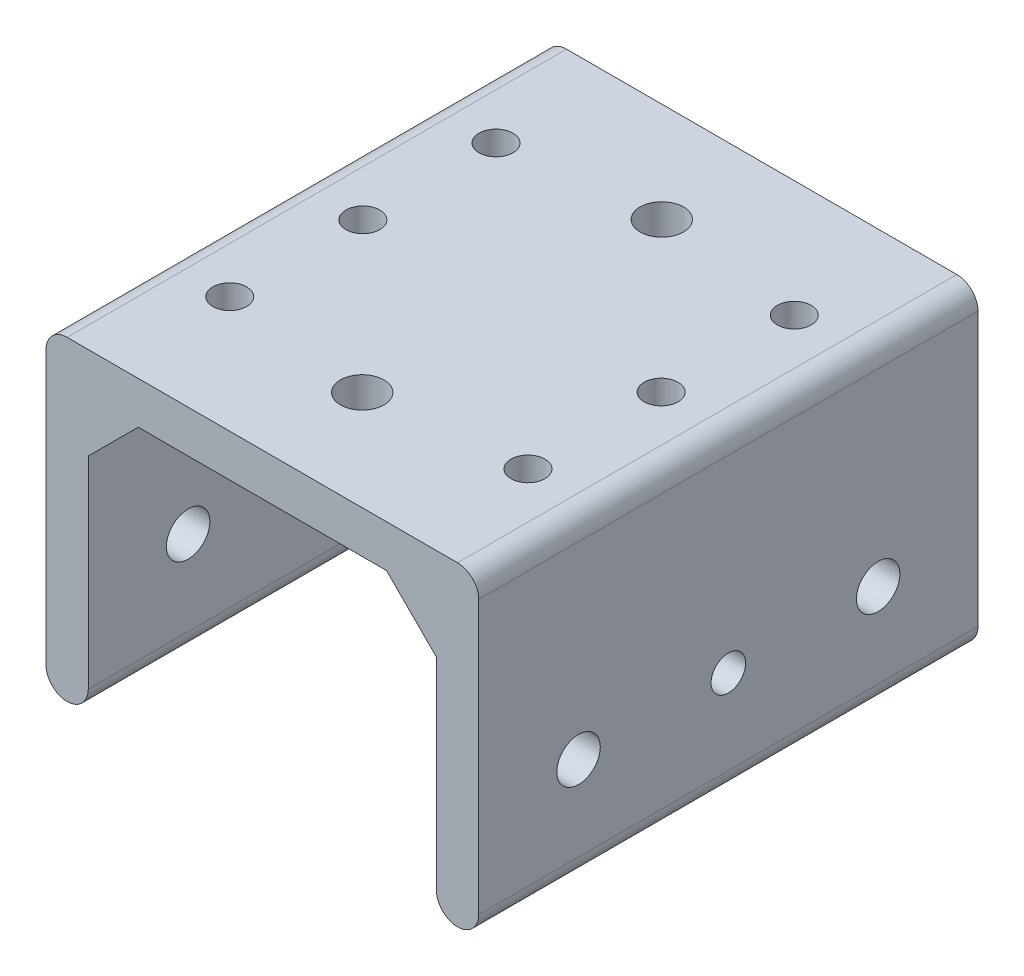
SolidWorks part; units mm, degrees
ref_plane "Front Plane" through (0, 0, 0) normal (0, 0, 1) x (1, 0, 0)
ref_plane "Top Plane" through (0, 0, 0) normal (0, 1, 0) x (1, 0, 0)
ref_plane "Right Plane" through (0, 0, 0) normal (1, 0, 0) x (0, 0, -1)
sketch "Sketch1" plane through (0, 0, 0) normal (0, 0, 1) x (1, 0, 0)
  line L0 (58.65, 33.52) -> (51.15, 41.02)
  line L1 (0, 0) -> (6.35, 0)
  line L2 (0, 0) -> (0, 41.02)
  line L4 (6.35, 0) -> (6.35, 33.52)
  line L5 (0, 0) -> (6.35, 41.02) construction
  line L6 (0, 41.02) -> (6.35, 0) construction
  line L7 (13.85, 41.02) -> (51.15, 41.02)
  line L8 (0, 41.02) -> (0, 47.37)
  line L9 (0, 47.37) -> (65, 47.37)
  line L10 (65, 41.02) -> (65, 47.37)
  line L11 (0, 41.02) -> (65, 47.37) construction
  line L12 (0, 47.37) -> (65, 41.02) construction
  line L14 (65, 41.02) -> (65, 0)
  line L15 (65, 0) -> (58.65, 0)
  line L16 (58.65, 33.52) -> (58.65, 0)
  line L17 (65, 41.02) -> (58.65, 0) construction
  line L18 (65, 0) -> (58.65, 41.02) construction
  line L19 (58.65, 41.02) -> (51.15, 41.02) construction
  line L20 (58.65, 41.02) -> (58.65, 33.52) construction
  line L21 (6.35, 33.52) -> (13.85, 41.02)
  line L22 (13.85, 41.02) -> (6.35, 41.02) construction
  line L23 (6.35, 41.02) -> (6.35, 33.52) construction
  point P4 (3.175, 20.51)
  point P9 (32.5, 44.195)
  point P13 (61.825, 20.51)
  dimension "D1" = 6.35
  dimension "D2" = 41.02
  dimension "D3" = 52.3
  dimension "D4" = 7.5
  dimension "D5" = 7.5
  dimension "D6" = 7.5
  dimension "D7" = 7.5
extrude "Boss-Extrude1" add sketch "Sketch1" along normal blind 75 contours L2 L8 L9 L10 L14 L15 L16 L0 L7 L21 L4 L1
sketch "Sketch2" plane through (0, 0, 0) normal (-1, 0, 0) x (0, 0, 1)
  line L0 (75, 41.02) -> (0, 41.02) construction
  line L1 (75, 41.02) -> (0, 41.02) construction
  line L2 (0, 15.87) -> (75, 15.87) construction
  line L3 (0, 0) -> (0, 47.37) construction
  line L4 (75, 0) -> (75, 47.37) construction
  line L5 (37.5, 0) -> (37.5, 47.37) construction
  line L6 (75, 0) -> (0, 0) construction
  line L7 (75, 47.37) -> (0, 47.37) construction
  point P2 (15, 15.87)
  point P15 (60, 15.87)
  dimension "D1" = 25.15
  dimension "D2" = 22.5
  dimension "D3" = 22.5
hole_wizard "5/16-18 Tapped Hole1" positions "Sketch3" profile "Sketch4" tap size "5/16-18" standard "ANSI Inch" end condition up to next
sketch "Sketch3" plane through (0, 0, 0) normal (-1, 0, 0) x (0, 0, 1)
  point P1 (60, 15.87)
  point P3 (15, 15.87)
sketch "Sketch4" plane through (0, 15.87, 60) normal (0, 1, 0) x (0, 0, 1)
  line L0 (0, 0) -> (0, 65)
  line L1 (0, 65) -> (3.2639, 65)
  line L2 (3.2639, 65) -> (3.2639, 0)
  line L5 (3.2639, 0) -> (0, 0)
  line L11 (0, -6.35) -> (0, 107.95) construction
  dimension "Thru Tap Drill Dia." = 6.5278
  dimension "Thru Tap Drill Depth" = 65
cosmetic thread "Hole Thread1" parameters "D2"=7.9375
cosmetic thread "Hole Thread2" parameters "D2"=7.9375
ref_plane "Plane1" through (32.5, 0, 0) normal (-1, 0, 0) x (0, 0, 1)
mirror "Mirror1" about plane through (32.5, 0, 0) normal (-1, 0, 0) of "5/16-18 Tapped Hole1"
sketch "Sketch5" plane through (0, 47.37, 0) normal (0, 1, 0) x (1, 0, 0)
  line L0 (32.5, -75) -> (32.5, 0) construction
  line L1 (0, -75) -> (65, -75) construction
  line L2 (0, 0) -> (65, 0) construction
  line L3 (0, -37.5) -> (65, -37.5) construction
  line L4 (0, -75) -> (0, 0) construction
  line L5 (65, -75) -> (65, 0) construction
  point P12 (32.5, -60)
  point P13 (32.5, -15)
  dimension "D1" = 22.5
  dimension "D2" = 22.5
hole_wizard "5/16-18 Tapped Hole2" positions "Sketch6" profile "Sketch7" tap size "5/16-18" standard "ANSI Inch" end condition up to next
sketch "Sketch6" plane through (0, 47.37, 0) normal (0, 1, 0) x (1, 0, 0)
  point P1 (32.5, -15)
  point P3 (32.5, -60)
sketch "Sketch7" plane through (32.5, 47.37, 15) normal (1, 0, 0) x (0, 0, 1)
  line L0 (0, 0) -> (0, 6.35)
  line L1 (0, 6.35) -> (3.2639, 6.35)
  line L2 (3.2639, 6.35) -> (3.2639, 0)
  line L5 (3.2639, 0) -> (0, 0)
  line L11 (0, -6.35) -> (0, 107.95) construction
  dimension "Thru Tap Drill Dia." = 6.5278
  dimension "Thru Tap Drill Depth" = 6.35
cosmetic thread "Hole Thread3" parameters "D2"=7.9375
cosmetic thread "Hole Thread4" parameters "D2"=7.9375
sketch "Sketch8" plane through (0, 0, 0) normal (-1, 0, 0) x (0, 0, 1)
  line L0 (18.2639, 15.87) -> (56.7361, 15.87) construction
  line L1 (37.5, 0) -> (37.5, 47.37) construction
  line L2 (75, 0) -> (0, 0) construction
  line L3 (75, 47.37) -> (0, 47.37) construction
  circle A0 centre (15, 15.87) radius 3.2639 construction
  circle A1 centre (60, 15.87) radius 3.2639 construction
  circle A2 centre (37.5, 15.87) radius 2.6
  dimension "D1" = 5.2
extrude "Cut-Extrude1" cut sketch "Sketch8" against normal through all contours A2
sketch "Sketch9" plane through (0, 47.37, 0) normal (0, 1, 0) x (1, 0, 0)
  line L0 (58.65, -75) -> (51.15, -75) construction
  line L1 (6.35, -75) -> (13.85, -75) construction
  line L2 (6.35, 0) -> (13.85, 0) construction
  line L3 (58.65, 0) -> (51.15, 0) construction
  line L4 (58.65, -75) -> (51.15, -75) construction
  line L5 (6.35, -75) -> (13.85, -75) construction
  line L6 (6.35, 0) -> (13.85, 0) construction
  line L7 (58.65, 0) -> (51.15, 0) construction
  line L8 (54.9, -75) -> (54.9, 0) construction
  line L9 (10.1, 0) -> (10.1, -75) construction
  line L10 (65, -37.5) -> (0, -37.5) construction
  line L11 (65, -75) -> (65, 0) construction
  line L12 (0, -75) -> (0, 0) construction
  circle A0 centre (54.9, -37.5) radius 3.2 construction
  circle A1 centre (54.9, -17.5) radius 3.2 construction
  circle A2 centre (54.9, -57.5) radius 3.2 construction
  dimension "D3" = 6.4
  dimension "D1" = 20
  dimension "D2" = 20
hole_wizard "1/4-20 Tapped Hole1" positions "Sketch10" profile "Sketch11" tap size "1/4-20" standard "ANSI Inch" end condition up to next
sketch "Sketch10" plane through (0, 47.37, 0) normal (0, 1, 0) x (1, 0, 0)
  point P0 (54.9, -57.5)
  point P3 (54.9, -37.5)
  point P6 (54.9, -17.5)
sketch "Sketch11" plane through (54.9, 47.37, 57.5) normal (1, 0, 0) x (0, 0, 1)
  line L0 (0, 0) -> (0, 13.851)
  line L1 (0, 13.851) -> (2.5527, 13.851)
  line L2 (2.5527, 13.851) -> (2.5527, 0)
  line L5 (2.5527, 0) -> (0, 0)
  line L11 (0, -6.35) -> (0, 107.95) construction
  dimension "Thru Tap Drill Dia." = 5.1054
  dimension "Thru Tap Drill Depth" = 13.851
cosmetic thread "Hole Thread5" parameters "D2"=6.35
cosmetic thread "Hole Thread6" parameters "D2"=6.35
cosmetic thread "Hole Thread7" parameters "D2"=6.35
mirror "Mirror2" about plane through (32.5, 0, 0) normal (-1, 0, 0) of "1/4-20 Tapped Hole1"
fillet "Fillet1" radius 3.175 6 edges at (58.65, 0, 37.5) (65, 0, 37.5) (0, 0, 37.5) (6.35, 0, 37.5) (0, 47.37, 37.5) (65, 47.37, 37.5)
